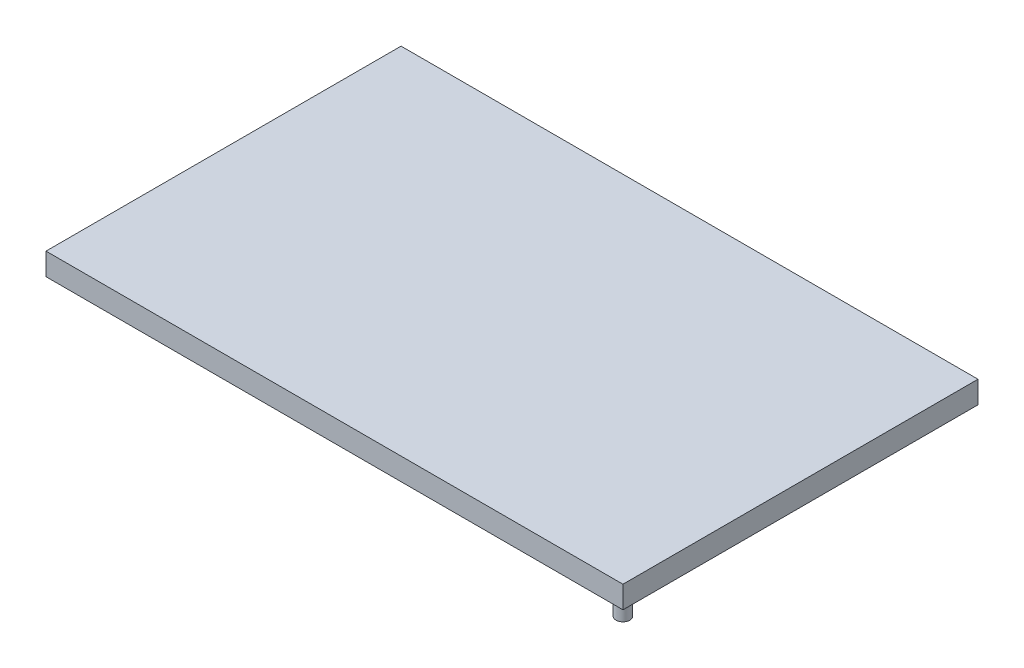
SolidWorks part; units mm, degrees
material "PET"
ref_plane "Alzado" through (0, 0, 0) normal (0, 0, 1) x (1, 0, 0)
ref_plane "Planta" through (0, 0, 0) normal (0, 1, 0) x (1, 0, 0)
ref_plane "Vista lateral" through (0, 0, 0) normal (1, 0, 0) x (0, 0, -1)
sketch "Croquis1" plane through (0, 0, 0) normal (0, 1, 0) x (1, 0, 0)
  line L1 (-100, 60) -> (100, 60)
  line L2 (-100, 60) -> (-100, -60)
  line L3 (-100, -60) -> (100, -60)
  line L4 (100, 60) -> (100, -60)
  line L5 (-100, 60) -> (100, -60) construction
  line L6 (-100, -60) -> (100, 60) construction
  line L7 (-104, 64) -> (104, 64)
  line L8 (-104, 64) -> (-104, -64)
  line L9 (-104, -64) -> (104, -64)
  line L10 (104, 64) -> (104, -64)
  line L11 (-104, 64) -> (104, -64) construction
  line L12 (-104, -64) -> (104, 64) construction
  point P0 (0, 0)
  point P6 (0, 0)
  dimension "D1" = 120
  dimension "D2" = 200
  dimension "D3" = 4
  dimension "D4" = 4
extrude "Saliente-Extruir1" add sketch "Croquis1" along normal blind 8 contours L10 L9 L8 L7
extrude "Cortar-Extruir1" cut sketch "Croquis1<4>" along normal blind 4 contours L4 L1 L2 L3 region at (0, 0, 0)
sketch "Croquis1<4>" plane through (0, 0, 0) normal (0, 1, 0) x (1, 0, 0) same geometry as "Croquis1"
sketch "Croquis2" plane through (0, 4, 0) normal (0, -1, 0) x (1, 0, 0)
  line L0 (100, -60) -> (100, 60) construction
  line L1 (-100, 60) -> (100, 60) construction
  line L2 (-100, -60) -> (100, -60) construction
  line L3 (-100, -60) -> (-100, 60) construction
  circle A0 centre (-90, -50) radius 2.5
  circle A1 centre (90, 50) radius 2.5
  dimension "D1" = 5
  dimension "D2" = 5
  dimension "D3" = 10
  dimension "D4" = 10
  dimension "D5" = 10
  dimension "D6" = 10
extrude "Saliente-Extruir2" add sketch "Croquis2" along normal blind 20
